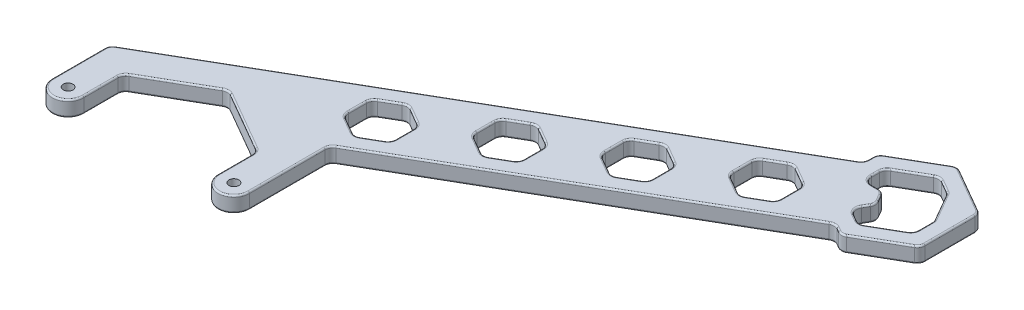
SolidWorks part; units mm, degrees
ref_plane "Front Plane" through (0, 0, 0) normal (0, 0, 1) x (1, 0, 0)
ref_plane "Top Plane" through (0, 0, 0) normal (0, 1, 0) x (1, 0, 0)
ref_plane "Right Plane" through (0, 0, 0) normal (1, 0, 0) x (0, 0, -1)
sketch "Sketch2" plane through (0, 0, 0) normal (0, 1, 0) x (1, 0, 0)
  line L0 (0, 0) -> (0, 50000) construction
  circle A0 centre (0, 0) radius 61.9125
  circle A1 centre (0, 0) radius 57.15 construction
  circle A2 centre (0, 57.15) radius 2
  circle A3 centre (5.1229, 56.9199) radius 2
  circle A4 centre (10.2045, 56.2316) radius 2
  circle A5 centre (15.204, 55.0905) radius 2
  circle A6 centre (20.0811, 53.5058) radius 2
  circle A7 centre (24.7965, 51.4904) radius 2
  circle A8 centre (29.3122, 49.0603) radius 2
  circle A9 centre (33.5919, 46.2353) radius 2
  circle A10 centre (37.6012, 43.038) radius 2
  circle A11 centre (41.3077, 39.4942) radius 2
  circle A12 centre (44.6817, 35.6324) radius 2
  circle A13 centre (47.6959, 31.4838) radius 2
  circle A14 centre (50.326, 27.0816) radius 2
  circle A15 centre (52.551, 22.4614) radius 2
  circle A16 centre (54.3529, 17.6603) radius 2
  circle A17 centre (55.7171, 12.7171) radius 2
  circle A18 centre (56.6328, 7.6714) radius 2
  circle A19 centre (57.0925, 2.564) radius 2
  circle A20 centre (57.0925, -2.564) radius 2
  circle A21 centre (56.6328, -7.6714) radius 2
  circle A22 centre (55.7171, -12.7171) radius 2
  circle A23 centre (54.3529, -17.6603) radius 2
  circle A24 centre (52.551, -22.4614) radius 2
  circle A25 centre (50.326, -27.0816) radius 2
  circle A26 centre (47.6959, -31.4838) radius 2
  circle A27 centre (44.6817, -35.6324) radius 2
  circle A28 centre (41.3077, -39.4942) radius 2
  circle A29 centre (37.6012, -43.038) radius 2
  circle A30 centre (33.5919, -46.2353) radius 2
  circle A31 centre (29.3122, -49.0603) radius 2
  circle A32 centre (24.7965, -51.4904) radius 2
  circle A33 centre (20.0811, -53.5058) radius 2
  circle A34 centre (15.204, -55.0905) radius 2
  circle A35 centre (10.2045, -56.2316) radius 2
  circle A36 centre (5.1229, -56.9199) radius 2
  circle A37 centre (0, -57.15) radius 2
  circle A38 centre (-5.1229, -56.9199) radius 2
  circle A39 centre (-10.2045, -56.2316) radius 2
  circle A40 centre (-15.204, -55.0905) radius 2
  circle A41 centre (-20.0811, -53.5058) radius 2
  circle A42 centre (-24.7965, -51.4904) radius 2
  circle A43 centre (-29.3122, -49.0603) radius 2
  circle A44 centre (-33.5919, -46.2353) radius 2
  circle A45 centre (-37.6012, -43.038) radius 2
  circle A46 centre (-41.3077, -39.4942) radius 2
  circle A47 centre (-44.6817, -35.6324) radius 2
  circle A48 centre (-47.6959, -31.4838) radius 2
  circle A49 centre (-50.326, -27.0816) radius 2
  circle A50 centre (-52.551, -22.4614) radius 2
  circle A51 centre (-54.3529, -17.6603) radius 2
  circle A52 centre (-55.7171, -12.7171) radius 2
  circle A53 centre (-56.6328, -7.6714) radius 2
  circle A54 centre (-57.0925, -2.564) radius 2
  circle A55 centre (-57.0925, 2.564) radius 2
  circle A56 centre (-56.6328, 7.6714) radius 2
  circle A57 centre (-55.7171, 12.7171) radius 2
  circle A58 centre (-54.3529, 17.6603) radius 2
  circle A59 centre (-52.551, 22.4614) radius 2
  circle A60 centre (-50.326, 27.0816) radius 2
  circle A61 centre (-47.6959, 31.4838) radius 2
  circle A62 centre (-44.6817, 35.6324) radius 2
  circle A63 centre (-41.3077, 39.4942) radius 2
  circle A64 centre (-37.6012, 43.038) radius 2
  circle A65 centre (-33.5919, 46.2353) radius 2
  circle A66 centre (-29.3122, 49.0603) radius 2
  circle A67 centre (-24.7965, 51.4904) radius 2
  circle A68 centre (-20.0811, 53.5058) radius 2
  circle A69 centre (-15.204, 55.0905) radius 2
  circle A70 centre (-10.2045, 56.2316) radius 2
  circle A71 centre (-5.1229, 56.9199) radius 2
  point P149 (0, 0)
  dimension "D1" = 123.825
  dimension "D2" = 114.3
  dimension "D3" = 4
  dimension "D4" = 70
sketch "Sketch1" plane through (0, 0, 0) normal (0, 1, 0) x (1, 0, 0)
  line L47 (0, -200000) -> (0, 250000) construction
  line L48 (33.5919, 26.841) -> (33.5919, 65.6296) construction
  line L49 (33.5919, 65.6296) -> (0, 85.0239) construction
  line L53 (0, 85.0239) -> (-33.5919, 65.6296) construction
  line L72 (-33.5919, 65.6296) -> (-33.5919, 26.841) construction
  line L73 (-33.5919, 26.841) -> (0, 7.4467) construction
  line L74 (0, 7.4467) -> (33.5919, 26.841) construction
  line L75 (0, 92.3563) -> (153.9793, 181.2563)
  line L76 (-39.9419, 69.2958) -> (-39.9419, 46.2353)
  line L79 (39.9419, 46.2353) -> (39.9419, 69.2958)
  line L80 (39.9419, 69.2958) -> (0, 92.3563)
  line L81 (0, 92.3563) -> (-39.9419, 69.2958)
  line L82 (-27.2419, 61.9635) -> (-27.2419, 46.2353)
  line L85 (27.2419, 46.2353) -> (27.2419, 61.9635)
  line L86 (27.2419, 61.9635) -> (0, 77.6916)
  line L87 (0, 77.6916) -> (-27.2419, 61.9635)
  line L88 (-26.3093, 29.9687) -> (0.4785, 14.5028) [skipped]
  line L89 (0.9327, 15.3175) -> (27.7204, 30.7835) [skipped]
  line L90 (-43.2479, 25.0835) -> (-1.5546, 1.0119) [skipped]
  line L91 (-3.306, -1.7944) -> (38.3874, 22.2773) [skipped]
  line L92 (31.75, 74.0254) -> (169.8543, 153.76)
  line L93 (153.9793, 181.2563) -> (169.8543, 153.76) construction
  line L94 (39.9419, 69.2958) -> (39.9419, 78.755)
  line L95 (153.9793, 162.9254) -> (195.2543, 186.7555) construction
  line L96 (195.2543, 186.7555) -> (174.6168, 198.6706)
  line L97 (174.6168, 198.6706) -> (153.9793, 186.7555)
  line L98 (153.9793, 186.7555) -> (153.9793, 162.9254)
  line L99 (153.9793, 162.9254) -> (174.6168, 151.0103)
  line L100 (174.6168, 151.0103) -> (195.2543, 162.9254)
  line L101 (195.2543, 162.9254) -> (195.2543, 186.7555)
  line L102 (160.3293, 183.0894) -> (160.3293, 166.5916)
  line L103 (160.3293, 166.5916) -> (174.6168, 158.3427)
  line L104 (174.6168, 158.3427) -> (188.9043, 166.5916)
  line L105 (188.9043, 166.5916) -> (188.9043, 183.0894)
  line L106 (188.9043, 183.0894) -> (174.6168, 191.3383)
  line L107 (174.6168, 191.3383) -> (160.3293, 183.0894)
  line L108 (168.0172, 174.8405) -> (171.317, 169.125)
  line L109 (171.317, 169.125) -> (167.4731, 162.4671)
  line L110 (168.0172, 174.8405) -> (160.3293, 174.8405)
  line L111 (181.7606, 187.2138) -> (188.9043, 174.8405)
  circle A0 centre (0, 46.2353) radius 33.5919 construction
  circle A1 centre (-33.5919, 46.2353) radius 6.35
  circle A2 centre (-33.5919, 46.2353) radius 2
  circle A3 centre (-33.5919, 46.2353) radius 2 construction
  circle A4 centre (33.5919, 46.2353) radius 2
  circle A5 centre (33.5919, 46.2353) radius 2 construction
  circle A6 centre (33.5919, 46.2353) radius 6.35
  circle A7 centre (174.6168, 174.8405) radius 20.6375 construction
  circle A8 centre (174.6168, 174.8405) radius 14.2875 construction
  point P67 (169.6671, 171.9827)
  dimension "D3" = 31.75
  dimension "D4" = 177.8
  dimension "D5" = 6.35
  dimension "D1" = 12.7
  dimension "D2" = 6.35
  dimension "D6" = 28.575
  dimension "D7" = 28.575
extrude "Boss-Extrude2" add sketch "Sketch1" along normal blind 6.35 contours L93 L75 L80 L92 | A6 L79 L80 L81 L76 A1 L82 L87 L86 L85 | A6 A4 | A1 A2 | L80 L94 L92 | L100 L101 L96 L97 L98 L99 L107 L106 L105 L104 L103 L102 | L108 L110 L102 L103 L109 | L106 L111 L105 region at (86.7083, 0, -124.4278) region at (15.4138, 0, -82.392) region at (154.6098, 0, -184.0059) region at (37.2113, 0, -74.0254) region at (-33.5919, 0, -52.4057) region at (33.5919, 0, -40.0649) region at (165.3233, 0, -169.4749) region at (186.5231, 0, -181.7146)
fillet "Fillet1" radius 3.175 22 edges at (-39.9419, 3.175, -69.2958) (27.2419, 3.175, -61.9635) (0, 3.175, -77.6916) (-27.2419, 3.175, -61.9635) (39.9419, 3.175, -78.755) (167.4731, 3.175, -162.4671) (160.3293, 3.175, -174.8405) (174.6168, 3.175, -158.3427) (188.9043, 3.175, -166.5916) (174.6168, 3.175, -191.3383) (160.3293, 3.175, -183.0894) (153.9793, 3.175, -181.2563) (153.9793, 3.175, -186.7555) (174.6168, 3.175, -198.6706) (195.2543, 3.175, -186.7555) (195.2543, 3.175, -162.9254) (174.6168, 3.175, -151.0103) (169.8543, 3.175, -153.76) (188.9043, 3.175, -174.8405) (181.7606, 3.175, -187.2138) (168.0172, 3.175, -174.8405) (171.317, 3.175, -169.125)
fillet "Fillet4" radius 0.635 96 edges at (40.3673, 6.35, -78.5094) (39.9419, 6.35, -61.5786) (33.5919, 6.35, -39.8853) (27.2419, 6.35, -53.1828) (26.8166, 6.35, -61.7179) (13.621, 6.35, -69.8275) (0, 6.35, -77.2004) (-13.621, 6.35, -69.8275) (-26.8166, 6.35, -61.7179) (-27.2419, 6.35, -53.1828) (-33.5919, 6.35, -39.8853) (-39.9419, 6.35, -56.849) (-39.5166, 6.35, -69.0502) (57.0187, 6.35, -125.276) (153.5539, 6.35, -181.5019) (153.9793, 6.35, -184.0059) (154.4047, 6.35, -186.51) (164.2981, 6.35, -192.7131) (174.6168, 6.35, -198.1794) (184.9356, 6.35, -192.7131) (194.8289, 6.35, -186.51) (195.2543, 6.35, -174.8405) (194.8289, 6.35, -163.171) (184.9356, 6.35, -156.9679) (174.6168, 6.35, -151.5015) (172.2356, 6.35, -152.3852) (169.8543, 6.35, -153.2688) (104.8981, 6.35, -116.2575) (-39.5166, 0, -69.0502) (-39.9419, 0, -56.849) (-33.5919, 0, -39.8853) (-27.2419, 0, -53.1828) (-26.8166, 0, -61.7179) (-13.621, 0, -69.8275) (0, 0, -77.2004) (13.621, 0, -69.8275) (26.8166, 0, -61.7179) (27.2419, 0, -53.1828) (33.5919, 0, -39.8853) (39.9419, 0, -61.5786) (40.3673, 0, -78.5094) (104.8981, 0, -116.2575) (169.8543, 0, -153.2688) (172.2356, 0, -152.3852) (174.6168, 0, -151.5015) (184.9356, 0, -156.9679) (194.8289, 0, -163.171) (195.2543, 0, -174.8405) (194.8289, 0, -186.51) (184.9356, 0, -192.7131) (174.6168, 0, -198.1794) (164.2981, 0, -192.7131) (154.4047, 0, -186.51) (153.9793, 0, -184.0059) (153.5539, 0, -181.5019) (57.0187, 0, -125.276) (181.6814, 0, -187.1346) (178.6141, 0, -189.0305) (174.6168, 0, -190.8471) (167.4731, 0, -187.2138) (160.7547, 0, -182.8438) (160.3293, 0, -179.6359) (161.2593, 0, -175.7704) (164.8442, 0, -174.8405) (167.7716, 0, -174.4151) (169.6671, 0, -171.9827) (170.8258, 0, -169.125) (169.7305, 0, -166.3771) (168.7434, 0, -162.8075) (171.626, 0, -160.0694) (174.6168, 0, -158.8339) (181.7606, 0, -162.4671) (188.4789, 0, -166.8372) (188.9043, 0, -171.2072) (188.7961, 0, -174.8115) (181.6814, 6.35, -187.1346) (178.6141, 6.35, -189.0305) (174.6168, 6.35, -190.8471) (167.4731, 6.35, -187.2138) (160.7547, 6.35, -182.8438) (160.3293, 6.35, -179.6359) (161.2593, 6.35, -175.7704) (164.8442, 6.35, -174.8405) (167.7716, 6.35, -174.4151) (169.6671, 6.35, -171.9827) (170.8258, 6.35, -169.125) (169.7305, 6.35, -166.3771) (168.7434, 6.35, -162.8075) (171.626, 6.35, -160.0694) (174.6168, 6.35, -158.8339) (181.7606, 6.35, -162.4671) (188.4789, 6.35, -166.8372) (188.9043, 6.35, -171.2072) (188.7961, 6.35, -174.8115) (185.3324, 0, -181.0272) (185.3324, 6.35, -181.0272)
sketch "Sketch3" plane through (0, 6.35, 0) normal (0, 1, 0) x (1, 0, 0)
  line L0 (238.769, 211.8788) -> (-43062.5012, -24788.1212) construction
  line L1 (-38.3544, 70.2123) -> (152.3918, 180.3397) construction
  line L2 (41.5294, 109.001) -> (32.0044, 103.5017)
  line L3 (32.0044, 103.5017) -> (32.0044, 92.5032)
  line L4 (32.0044, 92.5032) -> (41.5294, 87.0039)
  line L5 (41.5294, 87.0039) -> (51.0544, 92.5032)
  line L6 (51.0544, 92.5032) -> (51.0544, 103.5017)
  line L7 (51.0544, 103.5017) -> (41.5294, 109.001)
  line L9 (24.0669, 106.2513) -> (39.9419, 78.755) construction
  line L10 (0, 92.3563) -> (153.9793, 181.2563) construction
  circle A1 centre (41.5294, 98.0024) radius 9.525 construction
  dimension "D1" = 6.35
extrude "Cut-Extrude1" cut sketch "Sketch3" against normal through all
fillet "Fillet3" radius 3.175 6 edges at (32.0044, 3.175, -92.5032) (41.5294, 3.175, -87.0039) (51.0544, 3.175, -92.5032) (51.0544, 3.175, -103.5017) (41.5294, 3.175, -109.001) (32.0044, 3.175, -103.5017)
fillet "Fillet5" radius 0.635 24 edges at (50.6291, 0, -103.2561) (51.0544, 0, -98.0024) (50.6291, 0, -92.7488) (46.2919, 0, -89.7535) (41.5294, 0, -87.4951) (36.7669, 0, -89.7535) (32.4298, 0, -92.7488) (32.0044, 0, -98.0024) (32.4298, 0, -103.2561) (36.7669, 0, -106.2513) (41.5294, 0, -108.5098) (41.5294, 6.35, -108.5098) (46.2919, 6.35, -106.2513) (50.6291, 6.35, -103.2561) (51.0544, 6.35, -98.0024) (50.6291, 6.35, -92.7488) (46.2919, 6.35, -89.7535) (41.5294, 6.35, -87.4951) (36.7669, 6.35, -89.7535) (32.4298, 6.35, -92.7488) (32.0044, 6.35, -98.0024) (32.4298, 6.35, -103.2561) (46.2919, 0, -106.2513) (36.7669, 6.35, -106.2513)
pattern_linear "LPattern2" count 4 spacing 38.1 along (0.866, 0, -0.5) of "Cut-Extrude1", "Fillet3", "Fillet5"
sketch "Sketch4" plane through (-39.9914, 0, -69.2672) normal (-0.5, 0, -0.866) x (-0.866, 0, 0.5)
  line L0 (-222.1451, 0.635) -> (-1.8903, 0.635) construction
  line L1 (-222.1451, 5.715) -> (-75.4968, 5.715)
  line L2 (-222.1451, 5.715) -> (-222.1451, 0.635)
  line L3 (-222.1451, 0.635) -> (-75.4968, 0.635)
  line L4 (-75.4968, 5.715) -> (-75.4968, 0.635)
split line "Split Line1"
